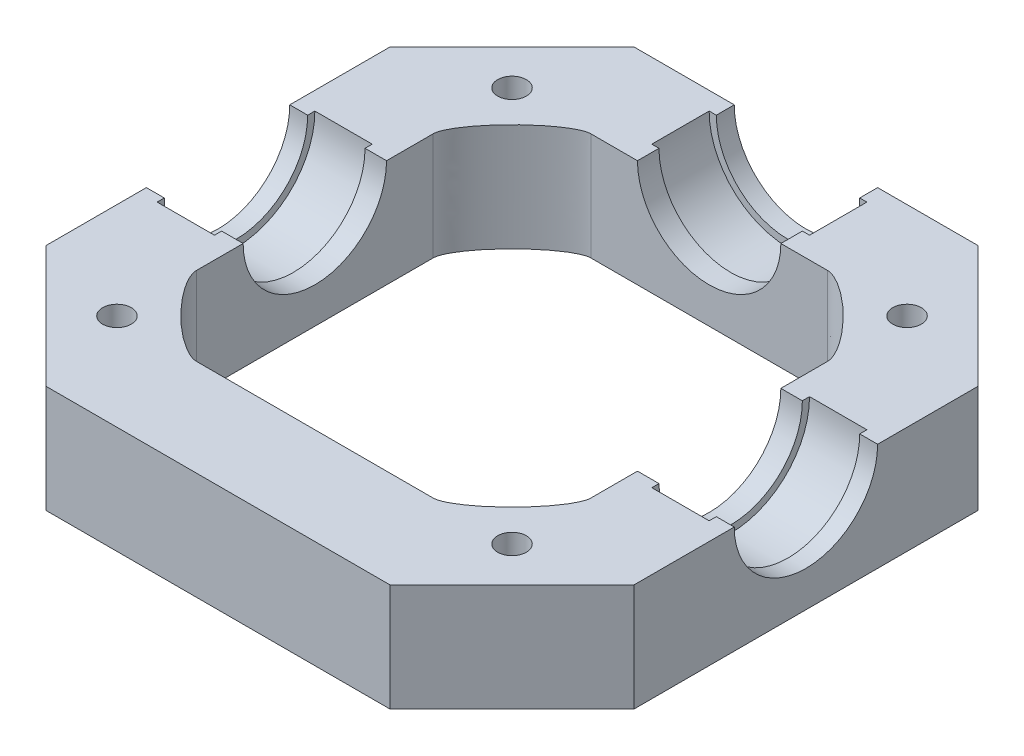
SolidWorks part; units mm, degrees
ref_plane "Front Plane" through (0, 0, 0) normal (0, 0, 1) x (1, 0, 0)
ref_plane "Top Plane" through (0, 0, 0) normal (0, 1, 0) x (1, 0, 0)
ref_plane "Right Plane" through (0, 0, 0) normal (1, 0, 0) x (0, 0, -1)
sketch "Sketch1" plane through (0, 0, 0) normal (0, 1, 0) x (1, 0, 0)
  line L1 (-27.5, 27.5) -> (27.5, 27.5)
  line L2 (-27.5, 27.5) -> (-27.5, -27.5)
  line L3 (-27.5, -27.5) -> (27.5, -27.5)
  line L4 (27.5, 27.5) -> (27.5, -27.5)
  line L5 (-27.5, 27.5) -> (27.5, -27.5) construction
  line L6 (-27.5, -27.5) -> (27.5, 27.5) construction
  line L7 (-41, 41) -> (41, 41)
  line L8 (-41, 41) -> (-41, -41)
  line L9 (-41, -41) -> (41, -41)
  line L10 (41, 41) -> (41, -41)
  line L11 (-41, 41) -> (41, -41) construction
  line L12 (-41, -41) -> (41, 41) construction
  point P0 (0, 0)
  point P5 (0, 0)
  dimension "D1" = 55
  dimension "D2" = 82
extrude "Boss-Extrude1" add sketch "Sketch1" against normal blind 15
ref_axis "Axis1" through (0, 0.75, 0) along (0, -1, 0)
sketch "Sketch2" plane through (0, 0, 0) normal (1, 0, 0) x (0, 0, -1)
  circle A0 centre (0, 0) radius 10
  dimension "D1" = 20
extrude "Cut-Extrude1" cut sketch "Sketch2" against normal through all from offset 0
sketch "Sketch3" plane through (0, 0, 0) normal (1, 0, 0) x (0, 0, -1)
  circle A0 centre (0, 0) radius 11
  dimension "D1" = 22
extrude "Cut-Extrude2" cut sketch "Sketch3" against normal blind 8 from offset 30.5 offset against normal yes
pattern_circular "CirPattern3" count 3 over 180 about axis through (0, 0.75, 0) along (0, -1, 0) of "Cut-Extrude1", "Cut-Extrude2"
fillet "Fillet1" radius 11 4 edges at (-27.5, -7.5, 27.5) (-27.5, -7.5, -27.5) (27.5, -7.5, 27.5) (27.5, -7.5, -27.5) conic rho 0.2
chamfer "Chamfer1" distance 17 angle 45 4 edges at (41, -7.5, 41) (-41, -7.5, 41) (-41, -7.5, -41) (41, -7.5, -41)
sketch "Sketch4" plane through (32.5, 0, -32.5) normal (0.7071, 0, -0.7071) x (-0.7071, 0, -0.7071)
  line L0 (0, 0) -> (0, -10) construction
  line L1 (0, 0.75) -> (0, -15.75) construction
  line L2 (-2, -10) -> (2, -10)
  line L3 (2, -10) -> (2, -11)
  line L4 (2, -11) -> (4, -11)
  line L5 (4, -11) -> (8, -15)
  line L6 (12.0208, -15) -> (-12.0208, -15) construction
  line L7 (8, -15) -> (-8, -15)
  line L8 (-2, -10) -> (-2, -11)
  line L9 (-2, -11) -> (-4, -11)
  line L10 (-4, -11) -> (-8, -15)
  point P16 (0, -15)
  dimension "D3" = 1
  dimension "D1" = 10
  dimension "D2" = 2
  dimension "D4" = 2
extrude "Cut-Extrude3" cut sketch "Sketch4" against normal mid plane 8 from offset 7 offset against normal yes
sketch "Sketch5" plane through (0, -10, 0) normal (0, -1, 0) x (1, 0, 0)
  line L0 (24.7218, -24.7218) -> (30.3787, -30.3787) construction
  line L1 (30.3787, -19.065) -> (19.065, -30.3787) construction
  line L2 (28.9645, -31.7929) -> (31.7929, -28.9645) construction
  circle A0 centre (27.5503, -27.5503) radius 2
  dimension "D1" = 4
extrude "Cut-Extrude4" cut sketch "Sketch5" against normal through all
pattern_circular "CirPattern4" count 4 over 360 about axis through (0, 0.75, 0) along (0, -1, 0) of "Cut-Extrude3", "Cut-Extrude4"
